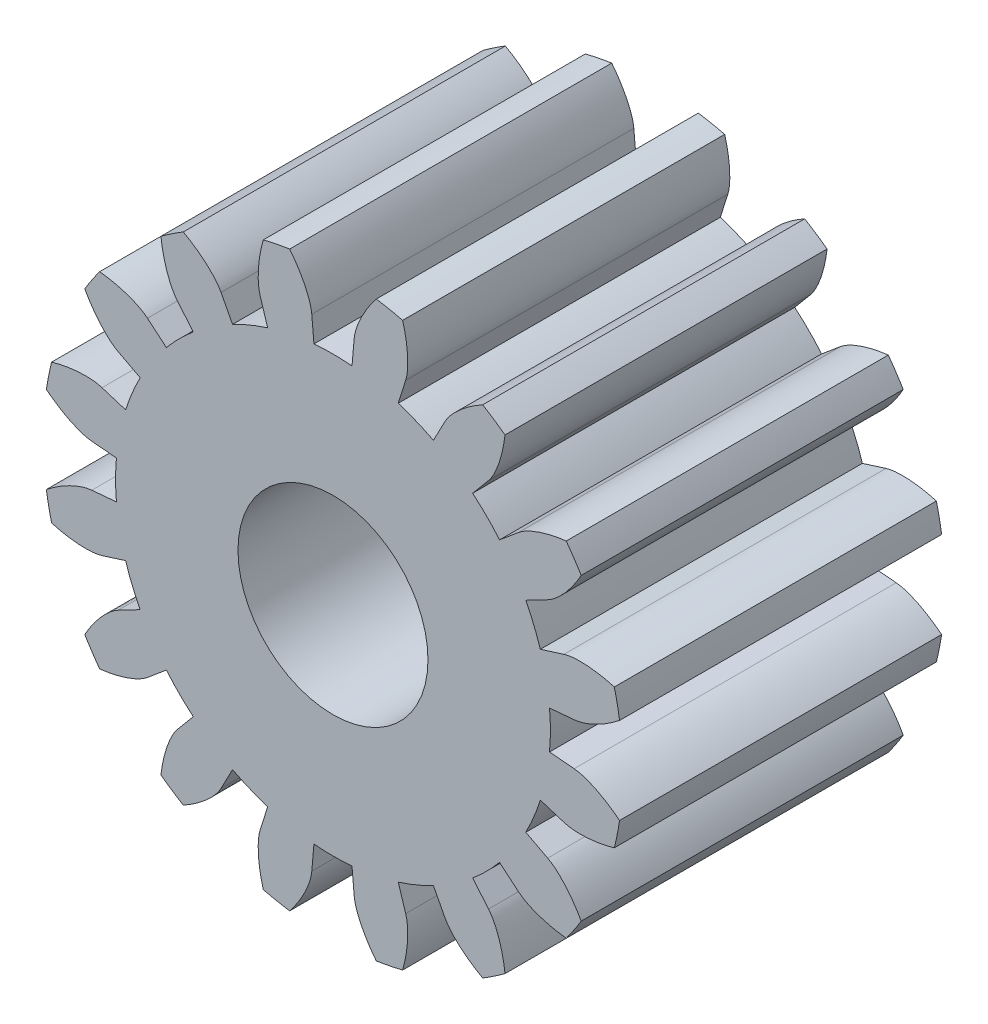
SolidWorks part; units mm, degrees
ref_plane "前视基准面" through (0, 0, 0) normal (0, 0, 1) x (1, 0, 0)
ref_plane "上视基准面" through (0, 0, 0) normal (0, 1, 0) x (1, 0, 0)
ref_plane "右视基准面" through (0, 0, 0) normal (1, 0, 0) x (0, 0, -1)
other "Configuration Table"
sketch "草图1" plane through (0, 0, 0) normal (0, 0, 1) x (1, 0, 0)
  line L0 (0, 0) -> (4, 0) construction
  line L1 (0, 0) -> (3.9807, 0.3921) construction
  line L2 (0, 0) -> (3.7443, 0.3291)
  line L3 (3.9807, 0.3921) -> (3.9807, -0.3921) construction
  line L4 (0, 0) -> (3.7443, -0.3291)
  circle A0 centre (0, 0) radius 4.5
  circle A1 centre (0, 0) radius 4 construction
  circle A2 centre (0, 0) radius 3.375
  circle A3 centre (0, 0) radius 3.7588 construction
  circle A4 centre (0, 0) radius 1.475
  spline S0 degree 4 poles (3.7443, 0.3291) (3.7729, 0.3316) (3.852, 0.3445) (3.9981, 0.3926) (4.2218, 0.5023) (4.4866, 0.6881) (4.7894, 0.9723) (5.0903, 1.3552) (5.3572, 1.8186) (5.6269, 2.4866) (5.7837, 3.1915) (5.8395, 3.939) (5.7839, 4.8292) (5.6145, 5.7064) (5.2709, 6.6864) (4.7256, 7.7028) (4.0402, 8.6299) (3.2362, 9.4556) (2.3338, 10.1718) (1.3511, 10.7732) (0.306, 11.2565) (-0.6502, 11.5751) (-1.4192, 11.7574) (-1.9866, 11.8556) (-2.3401, 11.9048) (-2.6306, 11.9368) (-2.9071, 11.9619) (-3.2112, 11.9792) (-3.4455, 11.9894) (-3.715, 11.9923) (-3.9867, 11.9914) (-4.2588, 11.9836) (-4.7357, 11.9589) (-5.1232, 11.9154) (-5.525, 11.8674) (-5.7188, 11.8311) (-5.8484, 11.8109) knots 0 0 0 0 0 0.005604 0.015718 0.02996 0.048734 0.068727 0.096889 0.125051 0.153212 0.209535 0.237696 0.271429 0.327752 0.384075 0.440398 0.496721 0.553044 0.609367 0.66569 0.722013 0.778336 0.806497 0.820578 0.834659 0.84874 0.86282 0.876901 0.890982 0.900036 0.909091 0.931818 0.954545 0.977273 1 1 1 1 1 construction
  spline S1 degree 4 poles (3.7443, 0.3291) (3.7729, 0.3316) (3.852, 0.3445) (3.9981, 0.3926) (4.2218, 0.5023) (4.4866, 0.6881) (4.7894, 0.9723) (5.0903, 1.3552) (5.3572, 1.8186) (5.6269, 2.4866) (5.7837, 3.1915) (5.8395, 3.939) (5.7839, 4.8292) (5.6145, 5.7064) (5.2709, 6.6864) (4.7256, 7.7028) (4.0402, 8.6299) (3.2362, 9.4556) (2.3338, 10.1718) (1.3511, 10.7732) (0.306, 11.2565) (-0.6502, 11.5751) (-1.4192, 11.7574) (-1.9866, 11.8556) (-2.3401, 11.9048) (-2.6306, 11.9368) (-2.9071, 11.9619) (-3.2112, 11.9792) (-3.4455, 11.9894) (-3.715, 11.9923) (-3.8743, 11.9918) (-3.9585, 11.9906) (-4.0005, 11.9898) knots 0 0 0 0 0 0.005604 0.015718 0.02996 0.048734 0.068727 0.096889 0.125051 0.153212 0.209535 0.237696 0.271429 0.327752 0.384075 0.440398 0.496721 0.553044 0.609367 0.66569 0.722013 0.778336 0.806497 0.820578 0.834659 0.84874 0.86282 0.876901 0.890982 0.900036 0.909091 0.909091 0.909091 0.909091 0.909091
  spline S2 degree 4 poles (3.7443, -0.3291) (3.7729, -0.3316) (3.852, -0.3445) (3.9981, -0.3926) (4.2218, -0.5023) (4.4866, -0.6881) (4.7894, -0.9723) (5.0903, -1.3552) (5.3572, -1.8186) (5.6269, -2.4866) (5.7837, -3.1915) (5.8395, -3.939) (5.7839, -4.8292) (5.6145, -5.7064) (5.2709, -6.6864) (4.7256, -7.7028) (4.0402, -8.6299) (3.2362, -9.4556) (2.3338, -10.1718) (1.3511, -10.7732) (0.306, -11.2565) (-0.6502, -11.5751) (-1.4192, -11.7574) (-1.9866, -11.8556) (-2.3401, -11.9048) (-2.6306, -11.9368) (-2.9071, -11.9619) (-3.2112, -11.9792) (-3.4455, -11.9894) (-3.715, -11.9923) (-3.9867, -11.9914) (-4.2588, -11.9836) (-4.7357, -11.9589) (-5.1232, -11.9154) (-5.525, -11.8674) (-5.7188, -11.8311) (-5.8484, -11.8109) knots 0 0 0 0 0 0.005604 0.015718 0.02996 0.048734 0.068727 0.096889 0.125051 0.153212 0.209535 0.237696 0.271429 0.327752 0.384075 0.440398 0.496721 0.553044 0.609367 0.66569 0.722013 0.778336 0.806497 0.820578 0.834659 0.84874 0.86282 0.876901 0.890982 0.900036 0.909091 0.931818 0.954545 0.977273 1 1 1 1 1 construction
  spline S3 degree 4 poles (3.7443, -0.3291) (3.7729, -0.3316) (3.852, -0.3445) (3.9981, -0.3926) (4.2218, -0.5023) (4.4866, -0.6881) (4.7894, -0.9723) (5.0903, -1.3552) (5.3572, -1.8186) (5.6269, -2.4866) (5.7837, -3.1915) (5.8395, -3.939) (5.7839, -4.8292) (5.6145, -5.7064) (5.2709, -6.6864) (4.7256, -7.7028) (4.0402, -8.6299) (3.2362, -9.4556) (2.3338, -10.1718) (1.3511, -10.7732) (0.306, -11.2565) (-0.6502, -11.5751) (-1.4192, -11.7574) (-1.9866, -11.8556) (-2.3401, -11.9048) (-2.6306, -11.9368) (-2.9071, -11.9619) (-3.2112, -11.9792) (-3.4455, -11.9894) (-3.715, -11.9923) (-3.8743, -11.9918) (-3.9585, -11.9906) (-4.0005, -11.9898) knots 0 0 0 0 0 0.005604 0.015718 0.02996 0.048734 0.068727 0.096889 0.125051 0.153212 0.209535 0.237696 0.271429 0.327752 0.384075 0.440398 0.496721 0.553044 0.609367 0.66569 0.722013 0.778336 0.806497 0.820578 0.834659 0.84874 0.86282 0.876901 0.890982 0.900036 0.909091 0.909091 0.909091 0.909091 0.909091
  point P15 (3.9807, 0)
  dimension "齿顶圆直径" = 9
  dimension "分度圆直径" = 8
  dimension "齿根圆直径" = 6.75
  dimension "基圆直径" = 7.5175
  dimension "内孔直径" = 2.95
  dimension "渐近线镜像线夹角" = 5.625
extrude "凸台-拉伸1" add sketch "草图1" along normal blind 5 contours A0 | A4
extrude "切除-拉伸1" cut sketch "草图1<3>" along normal through all contours A2 S3 A0 S1 region at (4.0116, 0, 0)
sketch "草图1<3>" plane through (0, 0, 0) normal (0, 0, 1) x (1, 0, 0) same geometry as "草图1"
pattern_circular "阵列(圆周)1" count 16 every 22.5 about axis through (0, 0, 5) along (0, 0, 1) of "切除-拉伸1"
equation "\"m\"= 0.5'模数"
equation "\"z\"= 16'齿数"
equation "\"a\"= 20度'压力角"
equation "\"d\"= \"m\" * \"z\"'分度圆直径"
equation "\"da\"= ( \"z\" + 2 ) * \"m\"'齿顶圆直径"
equation "\"df\"= ( \"z\" - 2.5 ) * \"m\"'齿根圆直径"
equation "\"s\"= 0.5 * PI * \"m\"'分度圆齿厚"
equation "\"r\"= 0.38 * \"m\"'齿根圆角"
equation "\"B\"= 0.3 * \"d\"'齿厚"
equation "\"db\"= \"m\" * \"z\" * cos ( \"a\" )'基圆直径"
equation "\"rb\"= \"db\" / 2'基圆半径"
equation "\"齿顶圆直径@草图1\"= \"da\""
equation "\"分度圆直径@草图1\"= \"d\""
equation "\"齿根圆直径@草图1\"= \"df\""
equation "\"基圆直径@草图1\"= \"db\""
equation "\"渐近线镜像线夹角@草图1\"= 360 / 4 / \"z\""
equation "\"h\"= 5'齿轮厚度"
equation "\"ir\"= 2.95'内孔直径"
equation "\"内孔直径@草图1\"= \"ir\""
equation "\"齿轮厚@凸台-拉伸1\"= \"h\""
equation "\"齿轮夹角@阵列(圆周)1\"= 360 / \"z\""
equation "\"齿数@阵列(圆周)1\"= \"z\""
